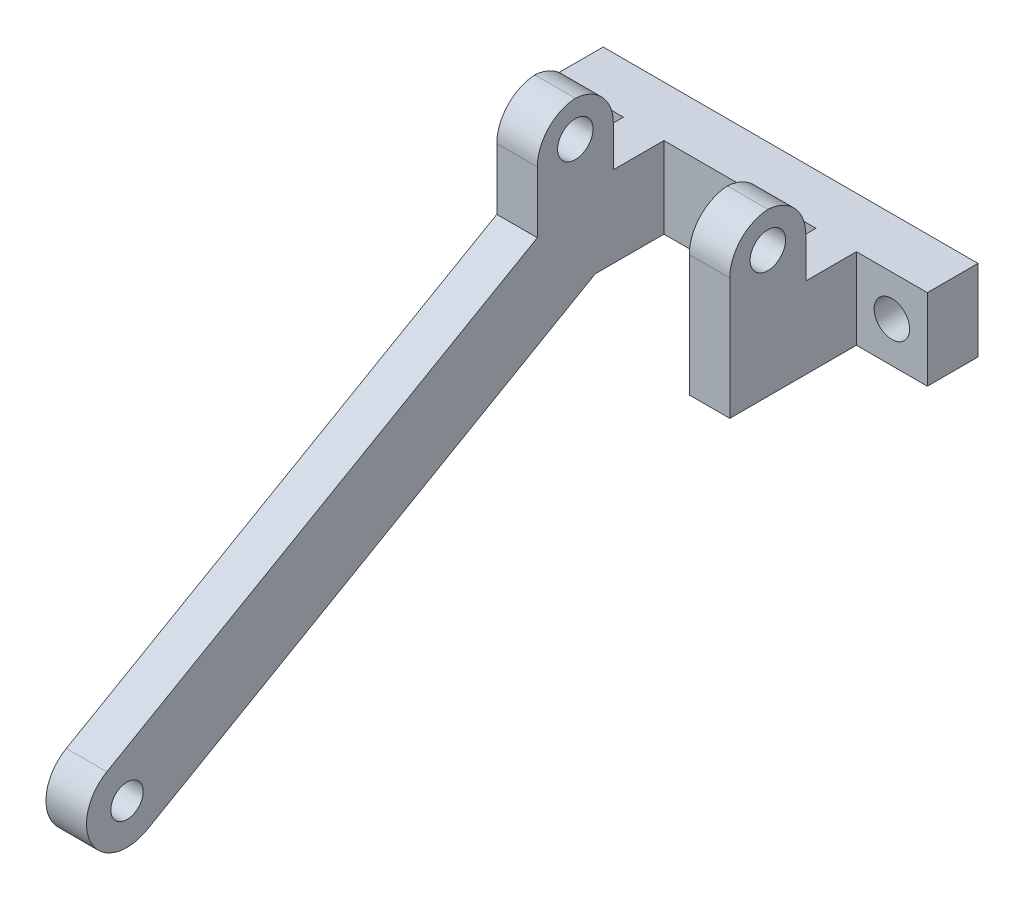
SolidWorks part; units mm, degrees
ref_plane "Front Plane" through (0, 0, 0) normal (0, 0, 1) x (1, 0, 0)
ref_plane "Top Plane" through (0, 0, 0) normal (0, 1, 0) x (1, 0, 0)
ref_plane "Right Plane" through (0, 0, 0) normal (1, 0, 0) x (0, 0, -1)
sketch "Sketch1" plane through (0, 0, 0) normal (0, 0, 1) x (1, 0, 0)
  line L0 (15, 0) -> (-15, 0) construction
  line L1 (-18.5, 4) -> (18.5, 4)
  line L2 (-18.5, 4) -> (-18.5, -4)
  line L3 (-18.5, -4) -> (18.5, -4)
  line L4 (18.5, 4) -> (18.5, -4)
  line L5 (-18.5, 4) -> (18.5, -4) construction
  line L6 (-18.5, -4) -> (18.5, 4) construction
  line L7 (0, -4) -> (0, 4) construction
  circle A0 centre (-15, 0) radius 1.75
  circle A1 centre (15, 0) radius 1.75
  point P0 (0, 0)
  point P12 (0, 0)
  dimension "D3" = 3.5
  dimension "D1" = 37
  dimension "D2" = 8
  dimension "D4" = 15
extrude "Boss-Extrude1" add sketch "Sketch1" along normal blind 5
sketch "Sketch2" plane through (0, 0, 5) normal (0, 0, 1) x (1, 0, 0)
  line L0 (0, 4) -> (0, -4) construction
  line L1 (18.5, 4) -> (-18.5, 4) construction
  line L2 (-18.5, -4) -> (18.5, -4) construction
  line L3 (11.5, -4) -> (7.5, 4) construction
  line L4 (-11.5, 4) -> (-7.5, 4)
  line L5 (-11.5, 4) -> (-11.5, -4)
  line L6 (-11.5, -4) -> (-7.5, -4)
  line L7 (-7.5, 4) -> (-7.5, -4)
  line L8 (-11.5, 4) -> (-7.5, -4) construction
  line L9 (-11.5, -4) -> (-7.5, 4) construction
  line L10 (11.5, 4) -> (7.5, -4) construction
  line L11 (7.5, 4) -> (7.5, -4)
  line L12 (11.5, -4) -> (7.5, -4)
  line L13 (11.5, 4) -> (11.5, -4)
  line L14 (11.5, 4) -> (7.5, 4)
  point P6 (-9.5, 0)
  point P15 (9.5, 0)
  dimension "D1" = 7.5
  dimension "D2" = 4
extrude "Boss-Extrude2" add sketch "Sketch2" along normal blind 12.5
sketch "Sketch4" plane through (0, 4, 0) normal (0, 1, 0) x (1, 0, 0)
  line L0 (-7.5, -17.5) -> (-7.5, -5) construction
  line L1 (-11.5, -17.5) -> (-7.5, -17.5)
  line L2 (-11.5, -17.5) -> (-11.5, -10)
  line L3 (-11.5, -10) -> (-7.5, -10)
  line L4 (-7.5, -17.5) -> (-7.5, -10)
  line L5 (0, 0) -> (0, -5) construction
  line L6 (7.5, -5) -> (-7.5, -5) construction
  line L7 (7.5, -17.5) -> (7.5, -10)
  line L8 (11.5, -10) -> (7.5, -10)
  line L9 (11.5, -17.5) -> (11.5, -10)
  line L10 (11.5, -17.5) -> (7.5, -17.5)
  dimension "D1" = 7.5
extrude "Boss-Extrude3" add sketch "Sketch4" along normal blind 8
sketch "Sketch3" plane through (-11.5, 0, 0) normal (-1, 0, 0) x (0, 0, 1)
  line L0 (10, 8.5) -> (17.5, 8.5) construction
  line L4 (10, 12) -> (10, 4) construction
  line L5 (17.5, 12) -> (17.5, -4) construction
  line L6 (13.75, 8.5) -> (13.75, 12) construction
  line L7 (10, 12) -> (17.5, 12) construction
  circle A0 centre (13.75, 8.5) radius 1.75
  dimension "D1" = 3.5
  dimension "D2" = 8.5
extrude "Cut-Extrude1" cut sketch "Sketch3" against normal through all
fillet "Fillet1" radius 4 4 edges at (-9.5, 12, 10) (9.5, 12, 10) (9.5, 12, 17.5) (-9.5, 12, 17.5)
sketch "Sketch5" plane through (-7.5, 0, 0) normal (1, 0, 0) x (0, 0, -1)
  line L0 (-10, 8) -> (-10, 4) construction
  line L1 (-10, 6.5) -> (-13, 6.5)
  line L2 (-10, 6.5) -> (-10, 1.5)
  line L3 (-10, 1.5) -> (-13, 1.5)
  line L4 (-13, 6.5) -> (-13, 1.5)
  line L5 (-10, 4) -> (-5, 4) construction
  dimension "D1" = 3
  dimension "D2" = 5
  dimension "D3" = 2.5
extrude "Boss-Extrude4" [suppressed] add sketch "Sketch5" along normal up to next
sketch "Sketch6" plane through (-11.5, 0, 0) normal (-1, 0, 0) x (0, 0, 1)
  line L0 (56.0113, -29.4012) -> (11.7824, -4)
  line L1 (17.5, -4) -> (5, -4) construction
  line L2 (11.7824, -4) -> (17.5, 1.9418)
  line L3 (13.75, 8.5) -> (58.0033, -25.9326) construction
  line L4 (17.5, 1.9418) -> (59.9954, -22.4639)
  line L5 (59.9954, -22.4639) -> (56.0113, -29.4012) construction
  line L6 (13.75, 8.5) -> (13.75, -4) construction
  line L7 (17.5, 8) -> (17.5, -4) construction
  circle A0 centre (58.0033, -25.9326) radius 1.6
  arc A1 (56.0113, -29.4012) -> (59.9954, -22.4639) centre (58.0033, -25.9326) ccw
  dimension "D1" = 3.2
  dimension "D2" = 8
  dimension "D3" = 52.114
  dimension "D4" = 56.071
  dimension "D5" = 1.9676
extrude "Boss-Extrude5" add sketch "Sketch6" against normal up to surface (4 mm away) up to face at (-7.5, 6.75, 13.75)
equation "\"X-ROD-SPACING\"=45"
equation "\"Y-ROD-SPACING\"=75"
equation "\"Z-ROD-SPACING\"=17.5"
equation "\"Y-BED-OFFSET\"=2"
equation "\"Y-BED-ROD-INSET\"=3.5"
equation "\"Y-BED-SCREW-SPACING\"=209"
equation "\"Y-BED-SCREW-CUTOUT-SLOT-HEIGHT\"=2"
equation "\"T-SLOT-NUT-FILLET-RADIUS\"=0.5"
equation "\"T-SLOT-SCREW-SHAFT-RADIUS\"=1.55"
equation "\"T-SLOT-SCREW-SHAFT-CUTOUT-LENGTH\"=11.0"
equation "\"T-SLOT-NUT-DEPTH\"=3.5"
equation "\"T-SLOT-NUT-WIDTH\"=2.85"
equation "\"T-SLOT-NUT-END-DISTANCE\"=8"
equation "\"ACRYLIC-THICKNESS\"=10"
equation "\"ACRYLIC-THICKNESS2\"=4.5"
equation "\"ACRYLIC-TAB-CUTOUT-SIZE\"=\"ACRYLIC-THICKNESS\"+\"ACRYLIC-TAB-TOLERANCE\"*2"
equation "\"ACRYLIC-TAB-TOLERANCE\"=-.05"
equation "\"ACRYLIC-TAB-WIDTH\"=\"ACRYLIC-THICKNESS\""
equation "\"ACRYLIC-M3-HOLE\"=2.9"
equation "\"SMOOTHROD-CAP-SCREW-DISTANCE\"=20"
equation "\"FRAME-WIDTH-INNER\"=370"
equation "\"NEMA17-HOLE-SPACING\"=31"
equation "\"NEMA17-CENTRAL-CUTOUT\"=22.5"
equation "\"Z-BRACKET-REACH\"=55"
equation "\"Z-ROD-INSET\"=16"
equation "\"TOP-BRACKET-SPACING\"=40"
equation "\"SMOOTHROD-X-LENGTH\"=350"
equation "\"SMOOTHROD-Y-LENGTH\"=350"
equation "\"SMOOTHROD-Z-LENGTH\"=350"
equation "\"SMOOTHROD-TIGHTENING-HEADROOM\"=.25"
equation "\"LEADSCREW-Z-LENGTH\"=300"
equation "\"SCREW-LENGTH-FRAME\"=\"ACRYLIC-THICKNESS\" + 10"
equation "\"SCREW-LENGTH-MOTOR\"=\"ACRYLIC-THICKNESS\" + 5"
equation "\"SCREW-LENGTH-EXTRUDER\"=28"
equation "\"SCREW-HEAD-RADIUS\"=6"
equation "\"PRINTED-X-SMOOTHROD-DIAMETER\"=8.4"
equation "\"PRINTED-X-SMOOTHROD-CUTOUT\"=10"
equation "\"PRINTED-X-BASE-HEIGHT\"=10"
equation "\"PRINTED-LM8UU-CUTOUT-SIZE\"=15.5"
equation "\"PRINTED-LM8UU-CUTOUT-LENGTH\"=24.5"
equation "\"PRINTED-X-IDLER-HEIGHT\"=16"
equation "\"PSU-MOUNTING-WIDTH\"=95"
equation "\"PSU-MOUNTING-HEIGHT\"=177"
equation "\"Y-BELT-TO-ROD-DISTANCE\"=20"
equation "\"SPOOL-HOLDER-ROD-SPACING\"=150"
equation "\"ACRYLIC-X-CARRIAGE-WIDTH\"=55"
equation "\"ACRYLIC-X-CARRIAGE-HEIGHT\"=75"
equation "\"ACRYLIC-X-CARRIAGE-LM8UU-CUTOUT-WIDTH\"=24.25"
equation "\"ACRYLIC-X-CARRIAGE-LM8UU-CUTOUT-HEIGHT\"=11.0"
equation "\"ACRYLIC-X-CARRIAGE-SCREW-SPACING-X\"=15"
equation "\"ACRYLIC-X-CARRIAGE-SCREW-SPACING-Y\"=33"
equation "\"ACRYLIC-X-CARRIAGE-CENTER-TAB-SPACING\"=14"
equation "\"ACRYLIC-X-CARRIAGE-EXTRUDER-OFFSET\"=26"
equation "\"ACRYLIC-X-CARRIAGE-EXTRUDER-ANGLE\"=90"
equation "\"ACRYLIC-X-CARRIAGE-EXTRUDER-SHELF-DEPTH\"=\"ACRYLIC-X-CARRIAGE-EXTRUDER-OFFSET\" + 28"
equation "\"ACRYLIC-X-CARRIAGE-EXTRUDER-BRACE-SPACING\"=23"
equation "\"ACRYLIC-X-CARRIAGE-EXTRUDER-BRACE-TAB-OFFSET\"=20"
equation "\"ACRYLIC-X-CARRIAGE-EXTRUDER-BRACE-HEIGHT\"=35"
equation "\"ACRYLIC-X-CARRIAGE-EXTRUDER-BRACE-SCREW-SPACING\"=22"
equation "\"ACRYLIC-X-CARRIAGE-DUAL-WIDTH-MULTIPLIER\"=1.65"
equation "\"ACRYLIC-X-CARRIAGE-DUAL-HOTEND-SPACING\"=42"
equation "\"ACRYLIC-X-CARRIAGE-DUAL-WIDTH\"=75"
equation "\"ACRYLIC-X-CARRIAGE-DUAL-HOTEND-SEPARATION\"=36"
equation "\"ACRYLIC-X-CARRIAGE-DUAL-MOUNT-PLATE-DEPTH\"=75"
equation "\"ACRYLIC-X-CARRIAGE-DUAL-MOUNT-BRACE-WIDTH\"=33"
equation "\"ACRYLIC-X-CARRIAGE-DUAL-MOUNT-SCREW-WIDTH\"=40"
equation "\"D3@Sketch1\"=3.5"
equation "\"PRINTED-M3-HOLE\"=3.5"
equation "\"BLOWER-FAN-WIDTH\"=15"
equation "\"D1@Sketch2\"=\"BLOWER-FAN-WIDTH\"/2"
